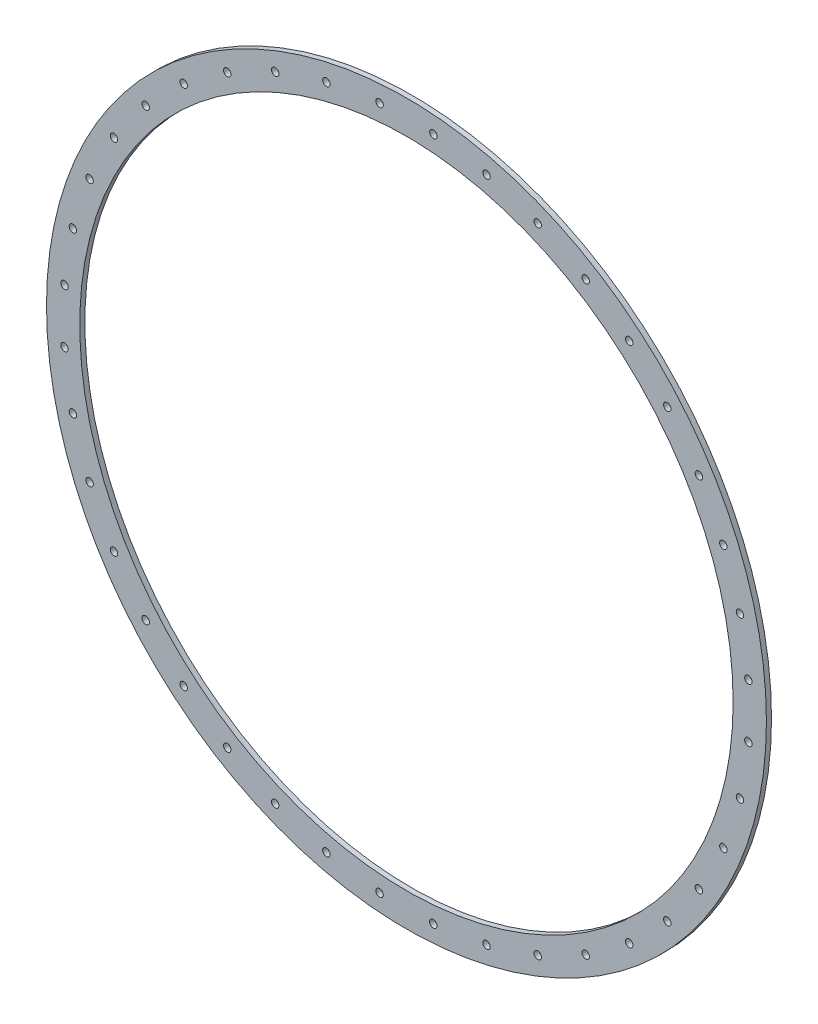
SolidWorks part; units mm, degrees
note: The reader was unsure of these and kept them because the rebuilt part matched: thickness of "Base-Flange1", "Sheet-Metal3", "Sheet-Metal4", "Sheet-Metal5".
material "A516-Gr 70"
ref_plane "Front Plane" through (0, 0, 0) normal (0, 0, 1) x (1, 0, 0)
ref_plane "Top Plane" through (0, 0, 0) normal (0, 1, 0) x (1, 0, 0)
ref_plane "Right Plane" through (0, 0, 0) normal (1, 0, 0) x (0, 0, -1)
sketch "Sketch1" plane through (0, 0, 0) normal (0, 0, 1) x (1, 0, 0)
  circle A0 centre (0, 0) radius 962
  circle A1 centre (0, 0) radius 1060
  dimension "D1" = 2120
  dimension "D2" = 1924
base flange "Base-Flange1" sketch "Sketch1" thickness 15 reverse thickness direction no parameters "D1"=0
sketch "Sketch2" plane through (0, 0, 0) normal (0, 0, 1) x (1, 0, 0)
  line L0 (0, 0) -> (79.2437, 1006.8865) construction
  line L1 (0, -962) -> (0, 962) construction
  circle A0 centre (79.2437, 1006.8865) radius 11
  circle A1 centre (0, 0) radius 962 construction
  point P11 (0, 0)
  dimension "D1" = 22
  dimension "D2" = 1010
  dimension "D3" = 4.5
extrude "Cut-Extrude1" cut sketch "Sketch2" against normal blind 20 normal cut yes
pattern_circular "CirPattern1" count 40 over 360 about axis through (0, 0, 0) along (0, 0, 1) of "Cut-Extrude1"
sketch "Bend-Lines1" [suppressed] plane through (0, 0, 0) normal (0, 1, 0) x (1, 0, 0)
sketch "Bounding-Box1" [suppressed] plane through (0, 0, 0) normal (0, 1, 0) x (1, 0, 0)
sheet metal parameters "Sheet-Metal3" thickness 15 parameters "D1"=0
flat pattern "Flat-Pattern3" [suppressed]
sketch "Bend-Lines2" plane through (0, 0, 0) normal (0, 1, 0) x (1, 0, 0)
sketch3d "Bounding-Box2" [suppressed]
  line L0 (999.2181, 1000.7809, 0) -> (1000.7806, -999.2182, 0) construction
  line L1 (-1000.7809, 999.2184, 0) -> (-999.2184, -1000.7807, 0) construction
  line L2 (999.2181, 1000.7809, 0) -> (-1000.7809, 999.2184, 0) construction
  line L3 (1000.7806, -999.2182, 0) -> (-999.2184, -1000.7807, 0) construction
sheet metal parameters "Sheet-Metal4" thickness 15 parameters "D1"=0, "D7"=10
flat pattern "Flat-Pattern3"
sketch "Bend-Lines2" plane through (0, 0, 0) normal (0, 1, 0) x (1, 0, 0)
sketch3d "Bounding-Box2" [suppressed]
  line L0 (999.2181, 1000.7809, 0) -> (1000.7806, -999.2182, 0) construction
  line L1 (-1000.7809, 999.2184, 0) -> (-999.2184, -1000.7807, 0) construction
  line L2 (999.2181, 1000.7809, 0) -> (-1000.7809, 999.2184, 0) construction
  line L3 (1000.7806, -999.2182, 0) -> (-999.2184, -1000.7807, 0) construction
sheet metal parameters "Sheet-Metal5" thickness 15 parameters "D1"=0, "D7"=10
flat pattern "Flat-Pattern3"
sketch "Bend-Lines2" plane through (0, 0, 0) normal (0, 1, 0) x (1, 0, 0)
sketch3d "Bounding-Box2" [suppressed]
  line L0 (1059.2182, 1060.7809, 0) -> (1060.7807, -1059.2183, 0) construction
  line L1 (-1060.7809, 1059.2184, 0) -> (-1059.2184, -1060.7808, 0) construction
  line L2 (1059.2182, 1060.7809, 0) -> (-1060.7809, 1059.2184, 0) construction
  line L3 (1060.7807, -1059.2183, 0) -> (-1059.2184, -1060.7808, 0) construction
